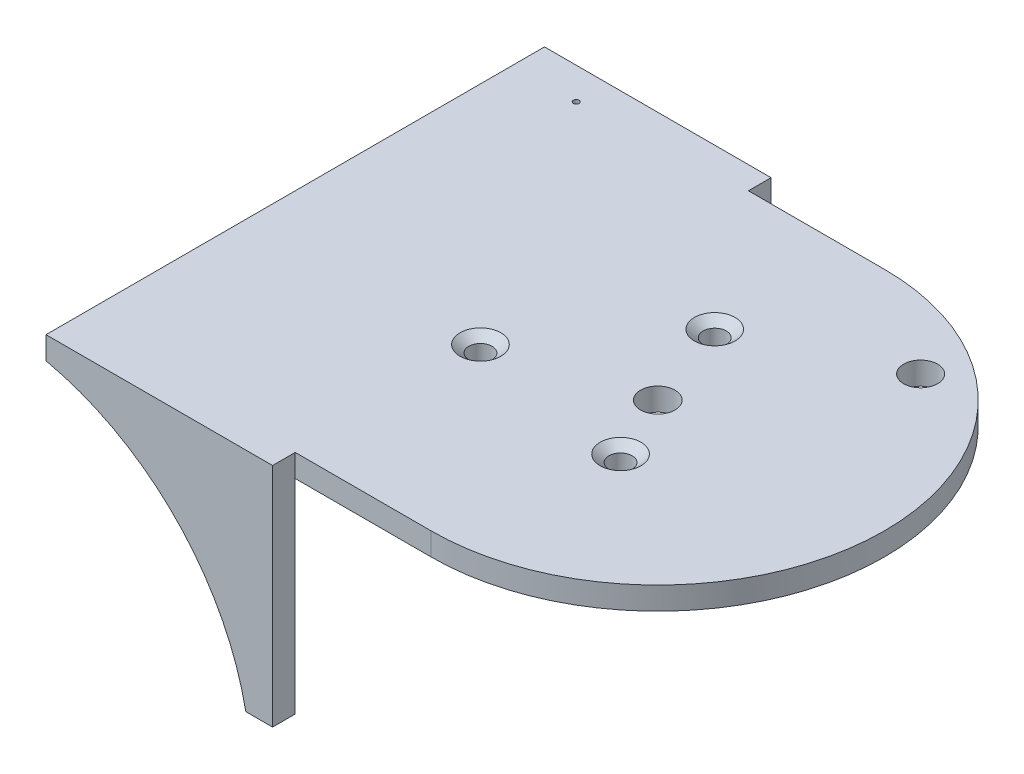
SolidWorks part; units mm, degrees
material "6061 Alloy"
ref_plane "Front Plane" through (0, 0, 0) normal (0, 0, 1) x (1, 0, 0)
ref_plane "Top Plane" through (0, 0, 0) normal (0, 1, 0) x (1, 0, 0)
ref_plane "Right Plane" through (0, 0, 0) normal (1, 0, 0) x (0, 0, -1)
sketch "Sketch1" plane through (0, 0, 0) normal (0, 1, 0) x (1, 0, 0)
  line L0 (0, 31.75) -> (-50.8, 31.75)
  line L1 (-50.8, 31.75) -> (-50.8, -31.75)
  line L2 (-50.8, -31.75) -> (0, -31.75)
  arc A0 (0, -31.75) -> (0, 31.75) centre (0, 0) ccw
  dimension "D1" = 63.5
  dimension "D2" = 50.8
extrude "Boss-Extrude1" add sketch "Sketch1" along normal blind 3.175
sketch "Sketch2" plane through (0, 3.175, 0) normal (0, 1, 0) x (1, 0, 0)
  circle A0 centre (0, 0) radius 2.413
  circle A1 centre (0, 0) radius 24.0538 construction
  circle A2 centre (-6.6548, 0) radius 17.399 construction
  circle A4 centre (-19.1658, -5.6802) radius 0.7937
  circle A5 centre (-4.6077, 12.5898) radius 0.7938
  circle A6 centre (3.9355, -9.1528) radius 0.7938
  circle A8 centre (3.9355, -9.1528) radius 1.2437 construction
  circle A10 centre (-19.1658, -5.6802) radius 1.0787 construction
  point P16 (-6.6127, -0.7477)
  dimension "D1" = 4.826
  dimension "D2" = 48.1076
  dimension "D3" = 34.798
  dimension "D5" = 1.5875
  dimension "D7" = 3
extrude "Cut-Extrude1" cut sketch "Sketch2" against normal through all
hole_wizard "CSK for #4 Flat Head Machine Screw (100)1" positions "Sketch4" profile "Sketch3" countersink size "#4" standard "ANSI Inch" end condition through all
sketch "Sketch4" plane through (0, 3.175, 0) normal (0, 1, 0) x (1, 0, 0)
  point P0 (3.9355, -9.1528)
  point P3 (-19.1658, -5.6802)
  point P6 (-4.6077, 12.5898)
sketch "Sketch3" plane through (3.9355, 3.175, 9.1528) normal (1, 0, 0) x (0, 0, 1)
  line L0 (0, 0) -> (0, 3.175)
  line L1 (0, 3.175) -> (1.6319, 3.175)
  line L2 (1.6319, 3.175) -> (1.6319, 1.0284)
  line L3 (1.6319, 1.0284) -> (2.8575, 0)
  line L5 (2.8575, 0) -> (0, 0)
  line L6 (-1.6319, 1.0284) -> (-2.8575, 0) construction
  line L11 (0, -6.35) -> (0, 107.95) construction
  dimension "Thru Hole Dia." = 3.2639
  dimension "Thru Hole Depth" = 3.175
  dimension "Near C'Sink Dia." = 5.715
  dimension "Near C'Sink Angle" = 100
sketch "Sketch5" plane through (0, 3.175, 0) normal (0, 1, 0) x (1, 0, 0)
  line L0 (0, 31.75) -> (-50.8, 31.75) construction
  circle A0 centre (15.24, 21.59) radius 2.3813
  circle A1 centre (-41.91, 30.48) radius 0.3969
  dimension "D1" = 4.7625
  dimension "D4" = 0.7937
  dimension "D2" = 15.24
  dimension "D3" = 21.59
  dimension "D5" = 1.27
  dimension "D6" = 8.89
extrude "Cut-Extrude2" cut sketch "Sketch5" against normal through all
sketch "Sketch6" plane through (0, 0, -31.75) normal (0, 0, -1) x (-1, 0, 0)
  line L0 (50.8, 3.175) -> (19.05, 3.175)
  line L1 (19.05, 3.175) -> (19.05, -28.575)
  line L2 (50.8, 3.175) -> (50.8, 0)
  line L4 (19.05, -28.575) -> (22.7993, -28.575)
  arc A0 (50.8, 0) -> (22.7993, -28.575) centre (58.6709, -35.7191) ccw
  dimension "D1" = 73.152
  dimension "D3" = 31.75
  dimension "D2" = 31.75
extrude "Boss-Extrude2" add sketch "Sketch6" along normal blind 3.175
mirror "Mirror1" about plane through (0, 0, 0) normal (0, 0, 1) of "Boss-Extrude2"
